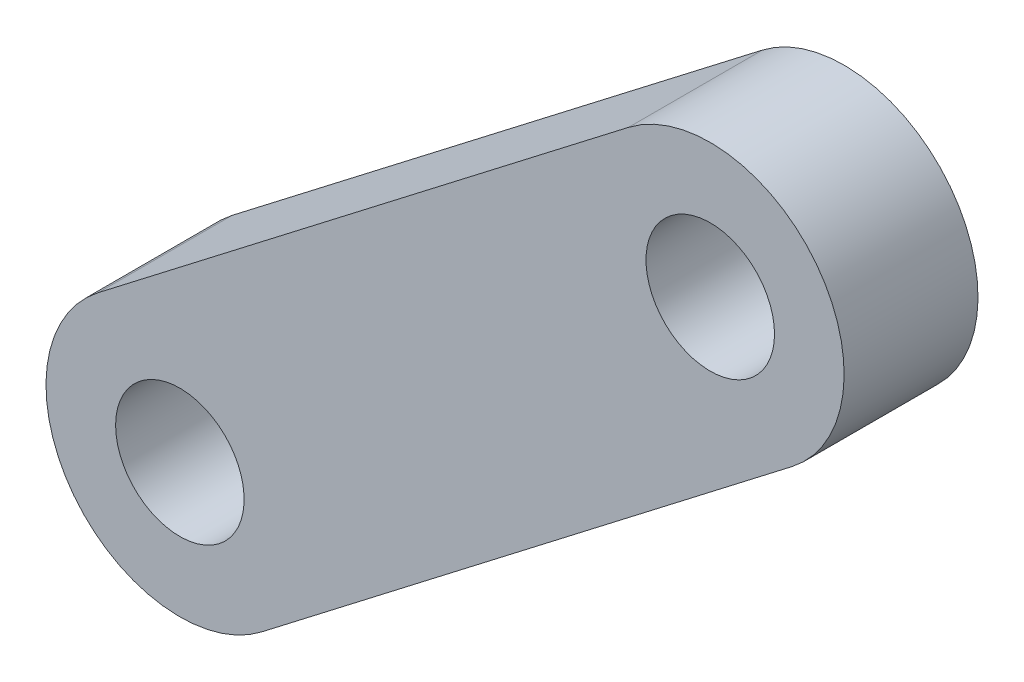
SolidWorks part; units mm, degrees
ref_plane "Front Plane" through (0, 0, 0) normal (0, 0, 1) x (1, 0, 0)
ref_plane "Top Plane" through (0, 0, 0) normal (0, 1, 0) x (1, 0, 0)
ref_plane "Right Plane" through (0, 0, 0) normal (1, 0, 0) x (0, 0, -1)
sketch "Sketch1" plane through (0, 0, 0) normal (0, 0, 1) x (0.9998, -0.022, 0)
  line L0 (-41.8829, 111.4723) -> (-17.0715, 91.626) construction
  line L1 (-1.7639, 79.3817) -> (-1.7639, 99.3817) construction
  line L2 (-1.7639, 99.3817) -> (-51.7712, 99.3817) construction
  line L3 (-46.2352, 83.6971) -> (-26.7675, 99.3817) construction
  line L4 (-46.2352, 83.6971) -> (-49.3722, 87.5906) construction
  line L5 (-49.3722, 87.5906) -> (-43.0983, 79.8035) construction
  line L6 (-49.3722, 87.5906) -> (-29.9044, 103.2753)
  line L7 (-43.0983, 79.8035) -> (-23.6306, 95.4882)
  line L8 (-29.9044, 103.2753) -> (-23.6306, 95.4882) construction
  circle A0 centre (-1.7639, 79.3817) radius 2.5 construction
  circle A1 centre (-1.7639, 79.3817) radius 2.5 construction
  circle A3 centre (-26.7675, 99.3817) radius 2.4
  arc A4 (-22.8629, 96.2585) -> (-30.6611, 96.2448) centre (-26.7675, 99.3817) ccw
  circle A6 centre (-46.2352, 83.6971) radius 1.5 construction
  arc A7 (-49.3722, 87.5906) -> (-43.0983, 79.8035) centre (-46.2352, 83.6971) ccw
  arc A8 (-23.6306, 95.4882) -> (-29.9044, 103.2753) centre (-26.7675, 99.3817) ccw
  point P18 (-26.7675, 99.3817)
  dimension "D1" = 5
  dimension "D2" = 5
  dimension "D4" = 4.8
  dimension "D5" = 3
  dimension "D6" = 10
  dimension "D3" = 20
  dimension "D7" = 25
extrude "Boss-Extrude1" add sketch "Sketch1" along normal blind 5 contours L7 A8 L6 A7 A3 A6 region at (-35.0532, 91.8768, 0)
sketch "Sketch2" plane through (0, 0, 0) normal (0, 0, -1) x (-1, 0, 0)
  circle A0 centre (44.3801, 84.6953) radius 2.4
  dimension "D1" = 4.8
extrude "Cut-Extrude1" cut sketch "Sketch2" against normal blind 5
sketch "Sketch4" plane through (0, 0, 0) normal (0, 0, -1) x (-1, 0, 0)
  line L0 (44.3801, 84.6953) -> (41.2108, 87.1357) construction
  line L1 (42.4785, 86.1595) -> (39.1522, 88.7207) construction
  line L2 (38.2371, 87.5322) -> (40.0673, 89.9092)
  line L3 (41.2108, 87.1357) -> (40.0673, 89.9092)
  line L4 (38.2371, 87.5322) -> (41.2108, 87.1357)
  line L5 (47.4305, 88.6571) -> (27.622, 103.909) construction
  circle A0 centre (44.3801, 84.6953) radius 2.4 construction
  point P10 (39.1522, 88.7207)
  dimension "D1" = 3
  dimension "D2" = 3
  dimension "D3" = 4
  dimension "D4" = 3
extrude "Cut-Extrude2" cut sketch "Sketch4" against normal blind 1
